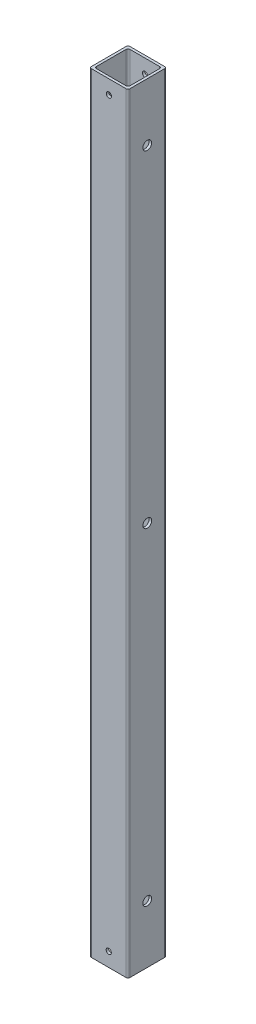
SolidWorks part; units mm, degrees
ref_plane "Front Plane" through (0, 0, 0) normal (0, 0, 1) x (1, 0, 0)
ref_plane "Top Plane" through (0, 0, 0) normal (0, 1, 0) x (1, 0, 0)
ref_plane "Right Plane" through (0, 0, 0) normal (1, 0, 0) x (0, 0, -1)
sketch "Sketch1" plane through (0, 0, 0) normal (0, 1, 0) x (1, 0, 0)
  line L0 (11.049, -11.049) -> (11.049, 11.049)
  line L1 (-12.7, -12.7) -> (12.7, -12.7)
  line L2 (-12.7, -12.7) -> (-12.7, 12.7)
  line L3 (-12.7, 12.7) -> (12.7, 12.7)
  line L4 (12.7, -12.7) -> (12.7, 12.7)
  line L5 (-12.7, -12.7) -> (12.7, 12.7) construction
  line L6 (-12.7, 12.7) -> (12.7, -12.7) construction
  line L7 (-11.049, 11.049) -> (11.049, 11.049)
  line L8 (-11.049, -11.049) -> (-11.049, 11.049)
  line L9 (-11.049, -11.049) -> (11.049, -11.049)
  point P0 (0, 0)
  dimension "D1" = 25.4
  dimension "D2" = 1.651
extrude "Boss-Extrude1" add sketch "Sketch1" along normal blind 508
fillet "Fillet1" radius 1.27 8 edges at (-12.7, 254, 12.7) (-12.7, 254, -12.7) (12.7, 254, -12.7) (12.7, 254, 12.7) (-11.049, 254, -11.049) (11.049, 254, 11.049) (11.049, 254, -11.049) (-11.049, 254, 11.049)
hole_wizard "#1 (0.228) Diameter Hole2" positions "Sketch4" profile "Sketch5" hole size "#1" standard "ANSI Inch" end condition through all
sketch "Sketch4" plane through (-12.7, 0, 0) normal (-1, 0, 0) x (0, 0, 1)
  line L3 (0, 0) -> (0, 508) construction
  line L4 (11.43, 508) -> (-11.43, 508) construction
  point P43 (0, 254)
  point P45 (0, 38.1)
  point P47 (0, 469.9)
  dimension "D1" = 215.9
  dimension "D2" = 215.9
sketch "Sketch5" plane through (-12.7, 469.9, 0) normal (0, 1, 0) x (0, 0, 1)
  line L0 (0, 0) -> (0, 25.4)
  line L1 (0, 25.4) -> (2.8956, 25.4)
  line L2 (2.8956, 25.4) -> (2.8956, 0)
  line L5 (2.8956, 0) -> (0, 0)
  line L11 (0, -6.35) -> (0, 107.95) construction
  dimension "Thru Hole Dia." = 5.7912
  dimension "Thru Hole Depth" = 25.4
hole_wizard "#8-32 Tapped Hole1" positions "Sketch6" profile "Sketch8" tap size "#8-32" standard "ANSI Inch" end condition through all
sketch "Sketch6" plane through (0, 0, 12.7) normal (0, 0, 1) x (1, 0, 0)
  line L1 (-11.43, 0) -> (11.43, 0) construction
  line L2 (-11.43, 508) -> (11.43, 508) construction
  point P5 (0, 9.271)
  point P15 (0.1031, 498.729)
  dimension "D1" = 9.271
  dimension "D2" = 9.271
sketch "Sketch8" plane through (0, 9.271, 12.7) normal (1, 0, 0) x (0, -1, 0)
  line L0 (0, 0) -> (0, 25.4)
  line L1 (0, 25.4) -> (1.7272, 25.4)
  line L2 (1.7272, 25.4) -> (1.7272, 0)
  line L5 (1.7272, 0) -> (0, 0)
  line L11 (0, -6.35) -> (0, 107.95) construction
  dimension "Thru Tap Drill Dia." = 3.4544
  dimension "Thru Tap Drill Depth" = 25.4
cosmetic thread "Hole Thread1" parameters "D2"=4.1656
cosmetic thread "Hole Thread2" parameters "D2"=4.1656
ref_plane "Plane1" through (-11.43, 508, 12.7) normal (1, 0, 0) x (0, 0, -1)
